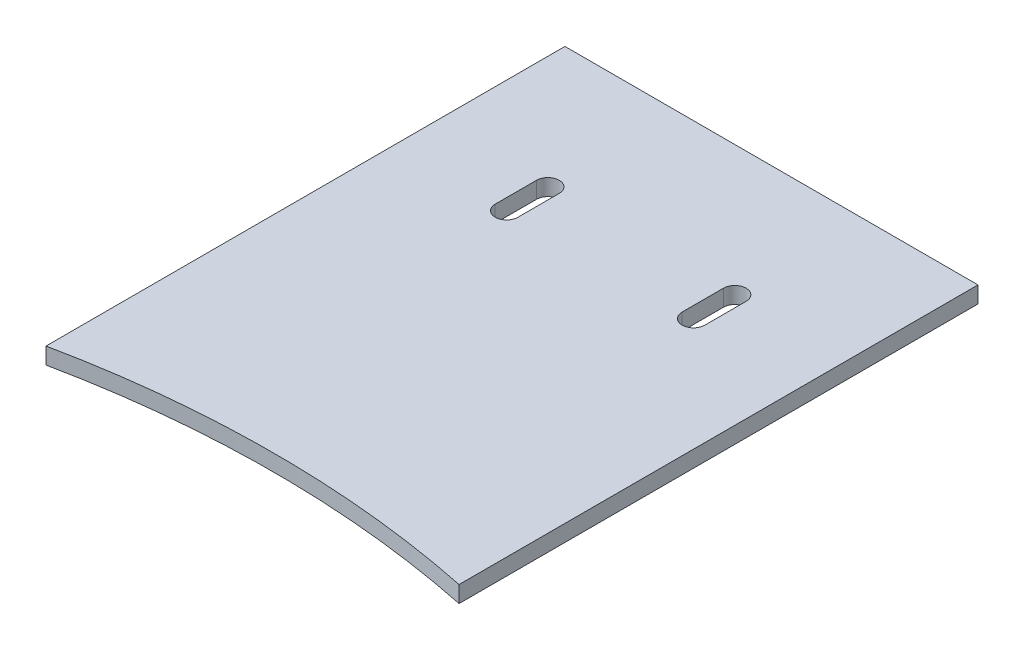
SolidWorks part; units mm, degrees
material "普通碳钢"
ref_plane "前视基准面" through (0, 0, 0) normal (0, 0, 1) x (1, 0, 0)
ref_plane "上视基准面" through (0, 0, 0) normal (0, 1, 0) x (1, 0, 0)
ref_plane "右视基准面" through (0, 0, 0) normal (1, 0, 0) x (0, 0, -1)
sketch "草图1" plane through (0, 0, 0) normal (0, 1, 0) x (1, 0, 0)
  line L0 (0, 0) -> (0, 1467.5) construction
  line L1 (-200, 1467.5) -> (200, 1467.5) construction
  line L2 (200, 1467.5) -> (200, 964.9924) construction
  line L3 (-200, 1467.5) -> (-200, 964.9924) construction
  line L4 (-200, 964.9924) -> (-200, 1467.5)
  line L5 (-200, 1467.5) -> (200, 1467.5)
  line L6 (200, 1467.5) -> (200, 964.9924)
  line L7 (-90.5, 1341.5) -> (-90.5, 1301.5) construction
  line L8 (-79.5, 1341.5) -> (-79.5, 1301.5)
  line L9 (-101.5, 1341.5) -> (-101.5, 1301.5)
  line L10 (90.5, 1301.5) -> (90.5, 1341.5) construction
  line L11 (79.5, 1301.5) -> (79.5, 1341.5)
  line L12 (101.5, 1301.5) -> (101.5, 1341.5)
  line L13 (-90.5, 1321.5) -> (90.5, 1321.5) construction
  circle A0 centre (0, 0) radius 985.5 construction
  arc A1 (-200, 964.9924) -> (200, 964.9924) centre (0, 0) cw
  arc A2 (-79.5, 1341.5) -> (-101.5, 1341.5) centre (-90.5, 1341.5) ccw
  arc A3 (-101.5, 1301.5) -> (-79.5, 1301.5) centre (-90.5, 1301.5) ccw
  arc A4 (79.5, 1301.5) -> (101.5, 1301.5) centre (90.5, 1301.5) ccw
  arc A5 (101.5, 1341.5) -> (79.5, 1341.5) centre (90.5, 1341.5) ccw
  point P5 (0, 0)
  point P12 (-90.5, 1321.5)
  point P18 (90.5, 1321.5)
  dimension "D1" = 1971
  dimension "D2" = 1467.5
  dimension "D3" = 400
  dimension "D4" = 200
  dimension "D5" = 22
  dimension "D6" = 40
  dimension "D7" = 181
  dimension "D8" = 1321.5
  dimension "D9" = 146
base flange "基体-法兰1" sketch "草图1" thickness 16 reverse thickness direction yes parameters "D1"=10
sketch "草图6" plane through (0, 16, 0) normal (0, 1, 0) x (1, 0, 0)
  line L0 (200, 1467.5) -> (-200, 1467.5) construction
  line L1 (-200, 1467.5) -> (200, 1467.5)
  line L2 (-200, 1467.5) -> (-200, 964.9924)
  line L3 (-200, 964.9924) -> (200, 964.9924)
  line L4 (200, 1467.5) -> (200, 964.9924)
  line L5 (-200, 1467.5) -> (-200, 964.9924) construction
  line L6 (200, 964.9924) -> (200, 1467.5) construction
  dimension "D1" = 400
  dimension "D2" = 502.5076
sketch "折弯-线1" plane through (0, 0, 0) normal (0, 1, 0) x (1, 0, 0)
sketch "边界框1" plane through (0, 0, 0) normal (0, 1, 0) x (1, 0, 0)
sheet metal parameters "钣金1" thickness 16 parameters "D1"=10
flat pattern "平板型式1" [suppressed]
sketch "折弯-线2" plane through (0, 0, 0) normal (0, 1, 0) x (1, 0, 0)
sketch "边界框2" [suppressed] plane through (0, 0, 0) normal (0, 1, 0) x (1, 0, 0)
